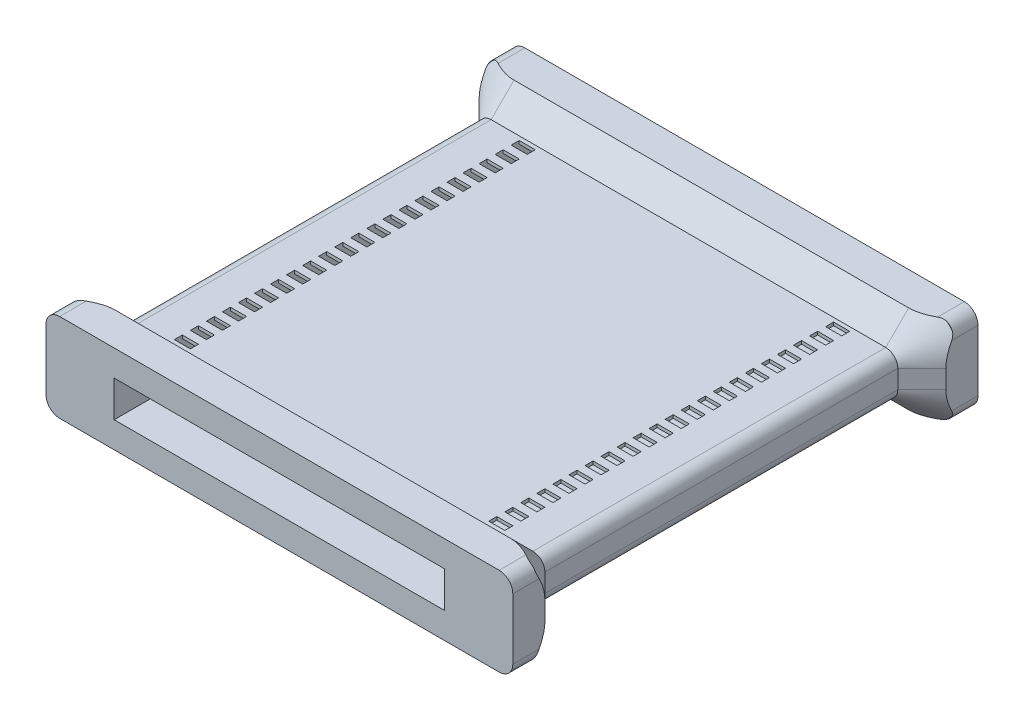
SolidWorks part; units mm, degrees
ref_plane "Front Plane" through (0, 0, 0) normal (0, 0, 1) x (1, 0, 0)
ref_plane "Top Plane" through (0, 0, 0) normal (0, 1, 0) x (1, 0, 0)
ref_plane "Right Plane" through (0, 0, 0) normal (1, 0, 0) x (0, 0, -1)
sketch "Sketch1" plane through (0, 0, 0) normal (0, 0, 1) x (1, 0, 0)
  line L1 (-20.6, 2.25) -> (20.6, 2.25)
  line L2 (-20.6, 2.25) -> (-20.6, -2.25)
  line L3 (-20.6, -2.25) -> (20.6, -2.25)
  line L4 (20.6, 2.25) -> (20.6, -2.25)
  line L5 (-20.6, 2.25) -> (20.6, -2.25) construction
  line L6 (-20.6, -2.25) -> (20.6, 2.25) construction
  line L7 (-29.1, 5.5) -> (29.1, 5.5)
  line L8 (-29.1, 5.5) -> (-29.1, -5.5)
  line L9 (-29.1, -5.5) -> (29.1, -5.5)
  line L10 (29.1, 5.5) -> (29.1, -5.5)
  line L11 (-29.1, 5.5) -> (29.1, -5.5) construction
  line L12 (-29.1, -5.5) -> (29.1, 5.5) construction
  point P0 (0, 0)
  point P6 (0, 0)
  dimension "D1" = 41.2
  dimension "D2" = 4.5
  dimension "D3" = 11
  dimension "D4" = 58.2
extrude "Boss-Extrude1" add sketch "Sketch1" along normal blind 58
sketch "Sketch2" plane through (0, 0, 58) normal (0, 0, 1) x (1, 0, 0)
  line L0 (20.6, 2.25) -> (-20.6, 2.25) construction
  line L1 (-26.1, 2.65) -> (26.1, 2.65)
  line L2 (-26.1, 2.65) -> (-26.1, -2.65)
  line L3 (-26.1, -2.65) -> (26.1, -2.65)
  line L4 (26.1, 2.65) -> (26.1, -2.65)
  line L5 (-26.1, 2.65) -> (26.1, -2.65) construction
  line L6 (-26.1, -2.65) -> (26.1, 2.65) construction
  line L7 (-29.1, 5.5) -> (-29.1, -5.5) construction
  point P0 (0, 0)
  dimension "D1" = 0.4
  dimension "D2" = 3
extrude "Cut-Extrude1" cut sketch "Sketch2" against normal offset from surface (52 mm away) 3 from offset 3 flip side to cut up to face at (0, 0, 0) offset against normal yes
fillet "Fillet1" radius 1.5 4 edges at (26.1, -2.65, 29) (26.1, 2.65, 29) (-26.1, -2.65, 29) (-26.1, 2.65, 29)
fillet "Fillet2" radius 1.7 8 edges at (29.1, -5.5, 1.5) (29.1, 5.5, 1.5) (29.1, -5.5, 56.5) (29.1, 5.5, 56.5) (-29.1, -5.5, 56.5) (-29.1, 5.5, 56.5) (-29.1, -5.5, 1.5) (-29.1, 5.5, 1.5)
chamfer "Chamfer1" distance 4 angle 45 16 edges at (0, -2.65, 3) (-25.6607, -2.2107, 3) (25.6607, -2.2107, 3) (-26.1, 0, 3) (26.1, 0, 3) (-25.6607, 2.2107, 3) (25.6607, 2.2107, 3) (0, 2.65, 3) (0, -2.65, 55) (25.6607, -2.2107, 55) (-25.6607, -2.2107, 55) (26.1, 0, 55) (-26.1, 0, 55) (25.6607, 2.2107, 55) (-25.6607, 2.2107, 55) (0, 2.65, 55)
sketch "Sketch4" plane through (0, 2.65, 0) normal (0, 1, 0) x (1, 0, 0)
  line L1 (-20.6, -49.5) -> (-18.6, -49.5)
  line L2 (-20.6, -49.5) -> (-20.6, -50.5)
  line L3 (-20.6, -50.5) -> (-18.6, -50.5)
  line L4 (-18.6, -49.5) -> (-18.6, -50.5)
  line L7 (20.6, -49.5) -> (18.6, -49.5)
  line L8 (20.6, -49.5) -> (20.6, -50.5)
  line L9 (20.6, -50.5) -> (18.6, -50.5)
  line L10 (18.6, -49.5) -> (18.6, -50.5)
  line L11 (-24.6, -51) -> (24.6, -51) construction
  dimension "D1" = 41.2
  dimension "D2" = 20.6
  dimension "D3" = 2
  dimension "D4" = 1
  dimension "D5" = 0.5
extrude "Cut-Extrude2" cut sketch "Sketch4" against normal through all
pattern_linear "LPattern1" count 22 spacing 2 along (0, 0, -1) of "Cut-Extrude2"
